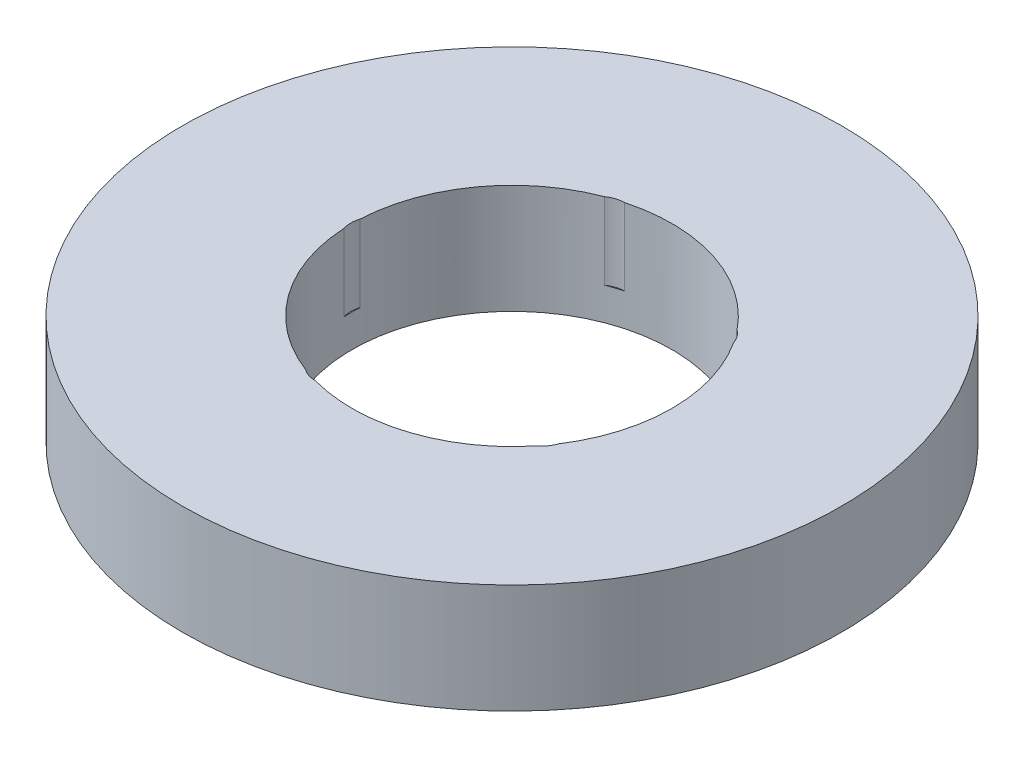
SolidWorks part; units mm, degrees
ref_plane "Front Plane" through (0, 0, 0) normal (0, 0, 1) x (1, 0, 0)
ref_plane "Top Plane" through (0, 0, 0) normal (0, 1, 0) x (1, 0, 0)
ref_plane "Right Plane" through (0, 0, 0) normal (1, 0, 0) x (0, 0, -1)
sketch "Sketch1" plane through (0, 0, 0) normal (0, 1, 0) x (1, 0, 0)
  circle A0 centre (0, 0) radius 87.5
  dimension "FLANGE_OD" = 175
extrude "Boss-Extrude1" add sketch "Sketch1" along normal blind 29
sketch "Sketch2" plane through (0, 0, 0) normal (0, 1, 0) x (1, 0, 0)
  circle A0 centre (0, 0) radius 42.5
  dimension "BORE_D" = 85
extrude "Cut-Extrude1" cut sketch "Sketch2" along normal through all
sketch "Sketch3" plane through (0, 29, 0) normal (0, 1, 0) x (1, 0, 0)
  circle A0 centre (0, 0) radius 35.7829 construction
  circle A1 centre (-35.7829, 0) radius 6.9942
  dimension "BOLT_D" = 13.9883
  dimension "BOLT_PCD" = 71.5658
extrude "Cut-Extrude2" cut sketch "Sketch3" against normal blind 20.3576
pattern_circular "CirPattern1" count 5 over 360 about axis through (0, 0, 0) along (0, 1, 0) of "Cut-Extrude2"
